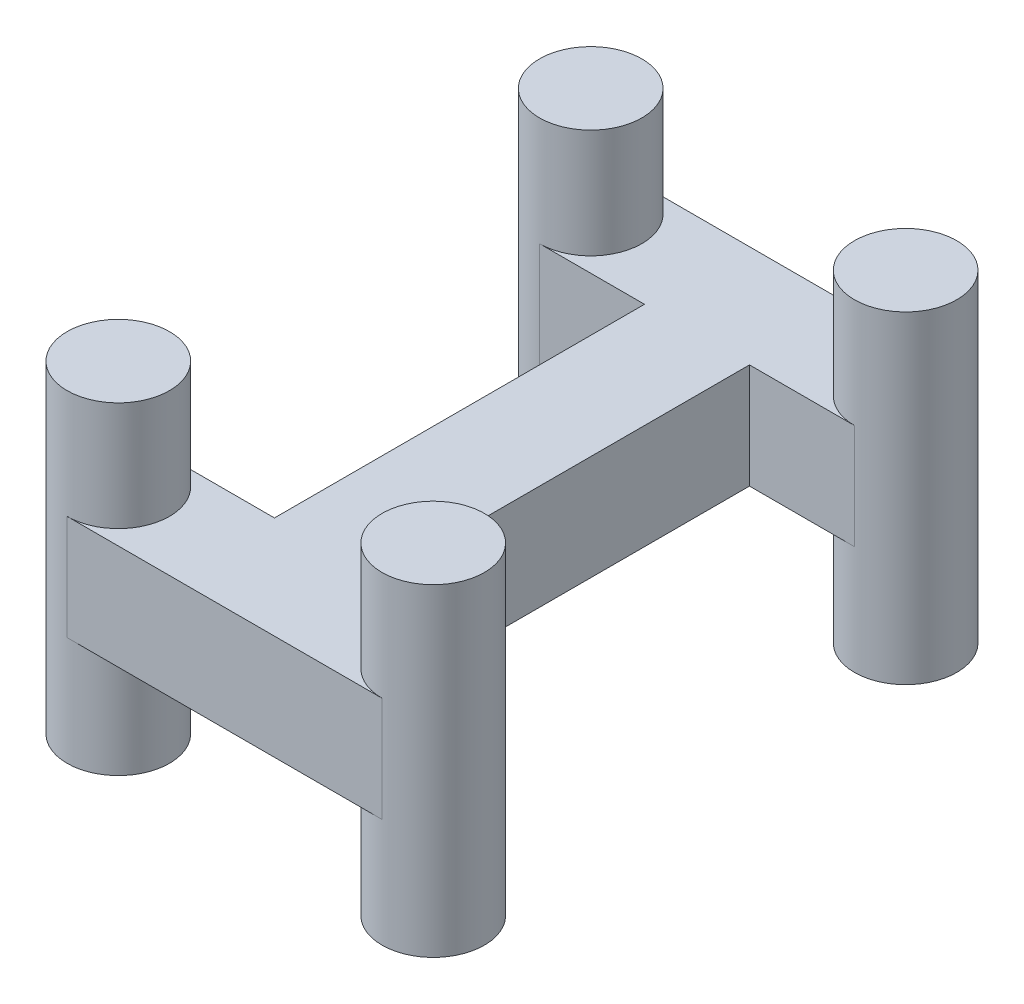
SolidWorks part; units mm, degrees
ref_plane "Front Plane" through (0, 0, 0) normal (0, 0, 1) x (1, 0, 0)
ref_plane "Top Plane" through (0, 0, 0) normal (0, 1, 0) x (1, 0, 0)
ref_plane "Right Plane" through (0, 0, 0) normal (1, 0, 0) x (0, 0, -1)
sketch "Sketch1" plane through (0, 0, 0) normal (0, 1, 0) x (1, 0, 0)
  line L0 (0, -10.95) -> (0, 10.95) construction
  line L1 (-6, -9) -> (6, -9) construction
  line L2 (-6, -9) -> (-6, 9) construction
  line L3 (-6, 9) -> (6, 9) construction
  line L4 (6, -9) -> (6, 9) construction
  line L5 (-6, -9) -> (6, 9) construction
  line L6 (-6, 9) -> (6, -9) construction
  line L7 (-6, -10.95) -> (6, -10.95)
  line L8 (6, -7.05) -> (2, -7.05)
  line L9 (-2, 7.05) -> (-2, -7.05)
  line L10 (-6, 7.05) -> (-2, 7.05)
  line L12 (6, 10.95) -> (-6, 10.95)
  line L13 (2, -7.05) -> (2, 7.05)
  line L14 (2, 7.05) -> (6, 7.05)
  line L15 (-2, -7.05) -> (-6, -7.05)
  circle A0 centre (-6, 9) radius 1.95
  circle A1 centre (6, 9) radius 1.95
  circle A2 centre (6, -9) radius 1.95
  circle A3 centre (-6, -9) radius 1.95
  point P0 (0, 0)
  point P24 (0, 0)
  dimension "D3" = 3.9
  dimension "D4" = 3.9
  dimension "D5" = 3.9
  dimension "D6" = 3.9
  dimension "D1" = 18
  dimension "D2" = 12
  dimension "D7" = 2
  dimension "D8" = 2
extrude "Boss-Extrude1" add sketch "Sketch1" along normal blind 2 and the other way blind 2 contours A3 L7 A2 L8 L13 L14 A1 L12 A0 L10 L9 L15 region at (0, 0, 0)
extrude "Boss-Extrude2" add sketch "Sketch1<4>" along normal blind 6.15 and the other way blind 6.15 contours A0 | A1 | A3 | A2 region at (-6, 0, 9) region at (6, 0, 9) region at (-6, 0, -9) region at (6, 0, -9)
sketch "Sketch1<4>" plane through (0, 0, 0) normal (0, 1, 0) x (1, 0, 0) same geometry as "Sketch1"
equation "\"2.5.00mm\"=10"
